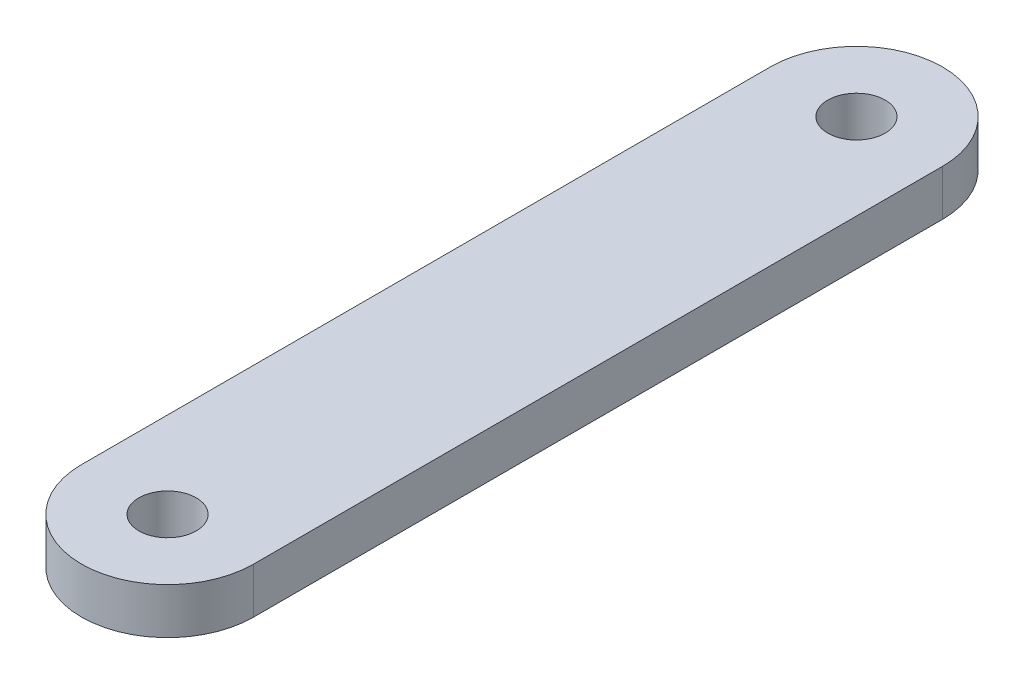
SolidWorks part; units mm, degrees
material "ABS"
ref_plane "Front Plane" through (0, 0, 0) normal (0, 0, 1) x (1, 0, 0)
ref_plane "Top Plane" through (0, 0, 0) normal (0, 1, 0) x (1, 0, 0)
ref_plane "Right Plane" through (0, 0, 0) normal (1, 0, 0) x (0, 0, -1)
sketch "Sketch1" plane through (0, 0, 0) normal (0, 1, 0) x (1, 0, 0)
  line L0 (0, 38.1) -> (0, 0) construction
  line L1 (4.7625, 38.1) -> (4.7625, 0)
  line L2 (-4.7625, 38.1) -> (-4.7625, 0)
  circle A0 centre (0, 0) radius 1.5875
  circle A1 centre (0, 38.1) radius 1.5875
  arc A2 (4.7625, 38.1) -> (-4.7625, 38.1) centre (0, 38.1) ccw
  arc A3 (-4.7625, 0) -> (4.7625, 0) centre (0, 0) ccw
  point P5 (0, 19.05)
  dimension "D1" = 3.175
  dimension "D2" = 3.175
  dimension "D3" = 38.1
  dimension "D4" = 9.525
extrude "Boss-Extrude1" add sketch "Sketch1" along normal blind 2.54
